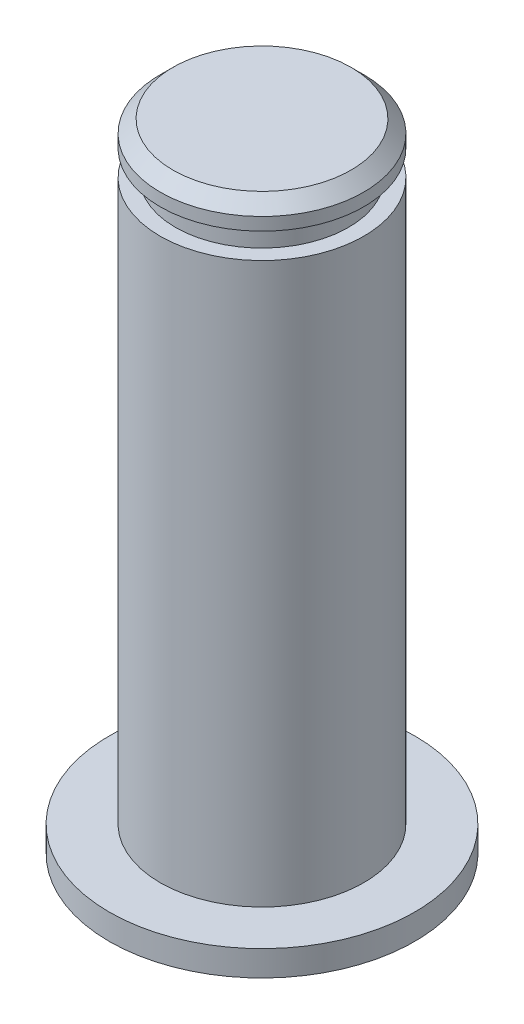
SolidWorks part; units mm, degrees
ref_plane "Спереди" through (0, 0, 0) normal (0, 0, 1) x (1, 0, 0)
ref_plane "Сверху" through (0, 0, 0) normal (0, 1, 0) x (1, 0, 0)
ref_plane "Справа" through (0, 0, 0) normal (1, 0, 0) x (0, 0, -1)
sketch "Эскиз1" plane through (0, 0, 0) normal (0, 0, 1) x (1, 0, 0)
  line L0 (-4, 25) -> (0, 25)
  line L1 (0, 25) -> (0, 0)
  line L2 (0, 0) -> (-6, 0)
  line L3 (-6, 0) -> (-6, 1)
  line L4 (-6, 1) -> (-4, 1)
  line L5 (-4, 1) -> (-4, 23)
  line L6 (-4, 23) -> (-3.4, 23)
  line L7 (-3.4, 23) -> (-3.4, 24)
  line L8 (-3.4, 24) -> (-4, 24)
  line L9 (-4, 24) -> (-4, 25)
  line L10 (0, 0) -> (0, -50000) construction
  line L11 (4, 23) -> (-4, 23) construction
  line L13 (4, 23) -> (-4, 23) construction
  line L15 (3.6, 24) -> (-3.6, 24) construction
  line L17 (3.6, 24) -> (-3.6, 24) construction
  point P4 (0, 0)
  point P14 (0, 0)
  point P15 (0, 0)
  point P16 (0, 0)
  point P19 (0, 0)
  dimension "D1" = 1
  dimension "D2" = 2
  dimension "D3" = 1
  dimension "D4" = 0.2
revolve "Повернуть1" add sketch "Эскиз1" angle 360 about L10
chamfer "Фаска1" distance 0.5 angle 45 1 edges at (0, 25, 4)
